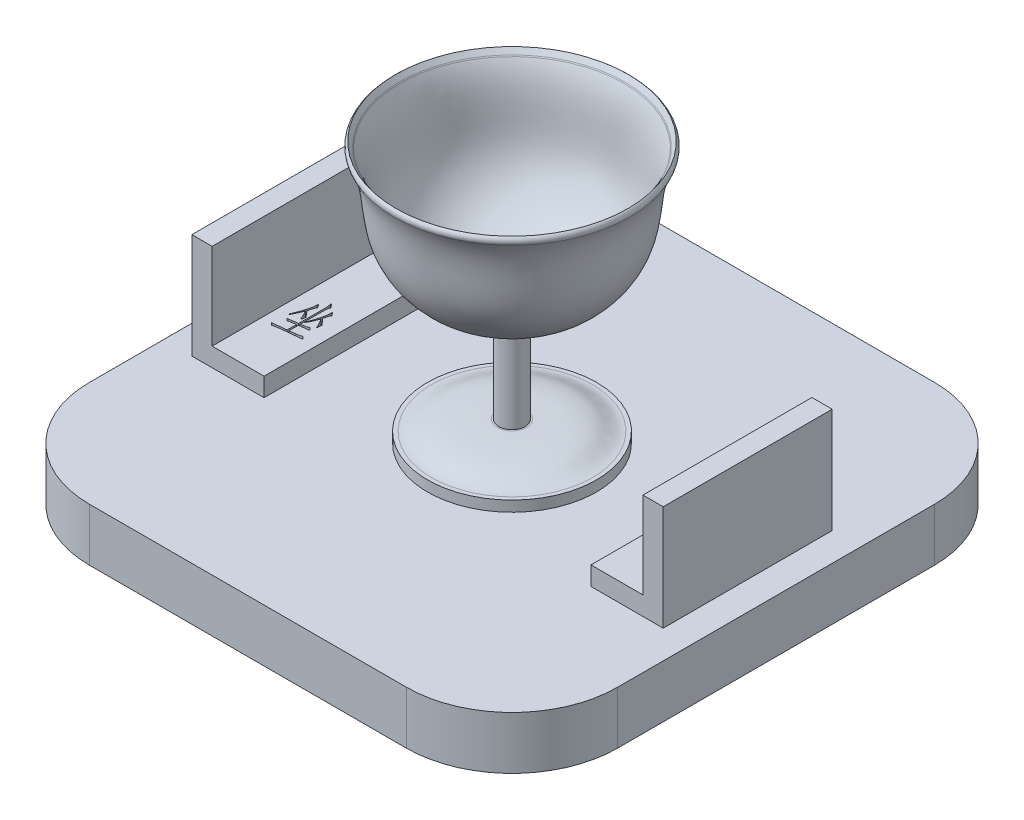
SolidWorks part; units mm, degrees
material "1023 碳钢板 (SS)"
ref_plane "前视基准面" through (0, 0, 0) normal (0, 0, 1) x (1, 0, 0)
ref_plane "上视基准面" through (0, 0, 0) normal (0, 1, 0) x (1, 0, 0)
ref_plane "右视基准面" through (0, 0, 0) normal (1, 0, 0) x (0, 0, -1)
sketch "草图1" plane through (0, 0, 0) normal (0, 1, 0) x (1, 0, 0)
  line L1 (-25, 25) -> (25, 25)
  line L2 (-25, 25) -> (-25, -25)
  line L3 (-25, -25) -> (25, -25)
  line L4 (25, 25) -> (25, -25)
  line L5 (0, -25) -> (0, 25) construction
  line L6 (-25, 0) -> (25, 0) construction
  point P0 (0, 0)
  dimension "D1" = 50
extrude "凸台-拉伸1" add sketch "草图1" along normal blind 5
sketch "草图3" plane through (0, 0, 0) normal (1, 0, 0) x (0, 0, -1)
  line L0 (-8, 5) -> (-7.2343, 5)
  line L1 (-25, 5) -> (25, 5) construction
  line L2 (-2.0783, 6) -> (0, 6)
  line L3 (0, 6) -> (0, 7)
  line L4 (0, 7) -> (-1.3915, 7)
  line L5 (-7.6284, 6) -> (-8, 6)
  line L6 (-8, 6) -> (-8, 5)
  spline S0 degree 3 poles (-7.2343, 5) (-6.3013, 5.5463) (-4.6264, 6.0383) (-2.7329, 6) (-2.0783, 6) knots 0 0 0 0 0.595969 1 1 1 1
  spline S1 degree 3 poles (-1.3915, 7) (-2.4339, 7) (-3.94, 7.0136) (-6.0449, 6.6499) (-7.0052, 6) (-7.6284, 6) knots 0 0 0 0 0.488087 0.71081 1 1 1 1
  dimension "D1" = 8
  dimension "D2" = 1
  dimension "D3" = 1
  dimension "D4" = 1
revolve "旋转1" add sketch "草图3" angle 360 about L3
sketch "草图4" plane through (0, 7, 0) normal (0, 1, 0) x (1, 0, 0)
  circle A0 centre (0, 0) radius 1.25
  dimension "D1" = 2.5
extrude "凸台-拉伸2" add sketch "草图4" along normal blind 10
sketch "草图5" plane through (0, 0, 0) normal (0, 0, 1) x (1, 0, 0)
  line L0 (0, 17) -> (-1.25, 17)
  line L1 (1.25, 17) -> (-1.25, 17) construction
  line L2 (-11.5949, 29.7574) -> (-10.9994, 29.7574)
  line L3 (0, 17.5) -> (-1.25, 17.5)
  line L5 (0, 17) -> (0, 17.5)
  line L6 (-11.5949, 29.7574) -> (-10.5757, 29.7574) construction
  line L7 (-10.6399, 29.2574) -> (-10.5757, 29.2574) construction
  spline S0 degree 3 poles (-1.25, 17) (-2.6301, 17) (-6.1352, 17.0578) (-10.9102, 22.437) (-9.7732, 27.5804) (-11.5949, 29.7574) knots 0 0 0 0 0.218482 0.565173 1 1 1 1
  spline S1 degree 1 poles (-1.25, 17.5) (-10.6399, 29.2574) knots 0 0 1 1 construction
  spline S2 degree 3 poles (-1.25, 17.5) (-1.6179, 17.5) (-2.364, 17.5035) (-3.7738, 17.5888) (-5.3742, 17.9596) (-7.0965, 19.1379) (-8.4794, 20.8352) (-9.2984, 22.7778) (-9.5691, 24.8868) (-9.7557, 26.7349) (-10.1264, 28.1919) (-10.4464, 28.9193) (-10.6399, 29.2574) knots 0 0 0 0 0.059486 0.118971 0.237942 0.356913 0.475884 0.594856 0.713827 0.832798 0.892283 0.951769 0.951769 0.951769 0.951769
  spline S3 degree 1 poles (-10.6399, 29.2574) (-10.9994, 29.7574) knots 0 0 1 1
  dimension "D1" = 0.5
revolve "旋转2" add sketch "草图5" angle 360 about L5
fillet "圆角1" radius 10 4 edges at (25, 2.5, -25) (-25, 2.5, -25) (25, 2.5, 25) (-25, 2.5, 25)
fillet "圆角4" radius 0.5 1 edges at (0, 29.7574, -11.5949)
fillet "圆角5" radius 1 1 edges at (0, 29.2574, -10.6399)
sketch "草图11" plane through (0, 0, 0) normal (0, 0, 1) x (1, 0, 0)
  line L0 (-15, 5) -> (-25, 5) construction
  line L1 (-22.3145, 14.9541) -> (-20.3954, 14.9541)
  line L2 (-22.3145, 14.9541) -> (-22.3145, 5)
  line L3 (-22.3145, 5) -> (-20.3954, 5)
  line L4 (-20.3954, 14.9541) -> (-20.3954, 5)
  line L5 (-21.355, 5) -> (-21.355, 14.9541) construction
  line L6 (-22.3145, 9.977) -> (-20.3954, 9.977) construction
  line L13 (-20.3954, 5) -> (-15.4763, 5)
  line L14 (-20.3954, 5) -> (-20.3954, 6.769)
  line L15 (-20.3954, 6.769) -> (-15.4763, 6.769)
  line L16 (-15.4763, 5) -> (-15.4763, 6.769)
  point P0 (-21.355, 9.977)
extrude "凸台-拉伸3" add sketch "草图11" along normal mid plane 16 contours L4 L1 L2 L3 | L13 L16 L15 L4 region at (-21.355, 9.977, 0) region at (-17.9359, 5.8845, 0)
mirror "镜向1" about plane through (0, 0, 0) normal (1, 0, 0) of "凸台-拉伸3"
sketch "草图12" plane through (0, 6.769, 0) normal (0, 1, 0) x (1, 0, 0)
  text T0 "坐"
extrude "切除-拉伸2" cut sketch "草图12" against normal blind 1
